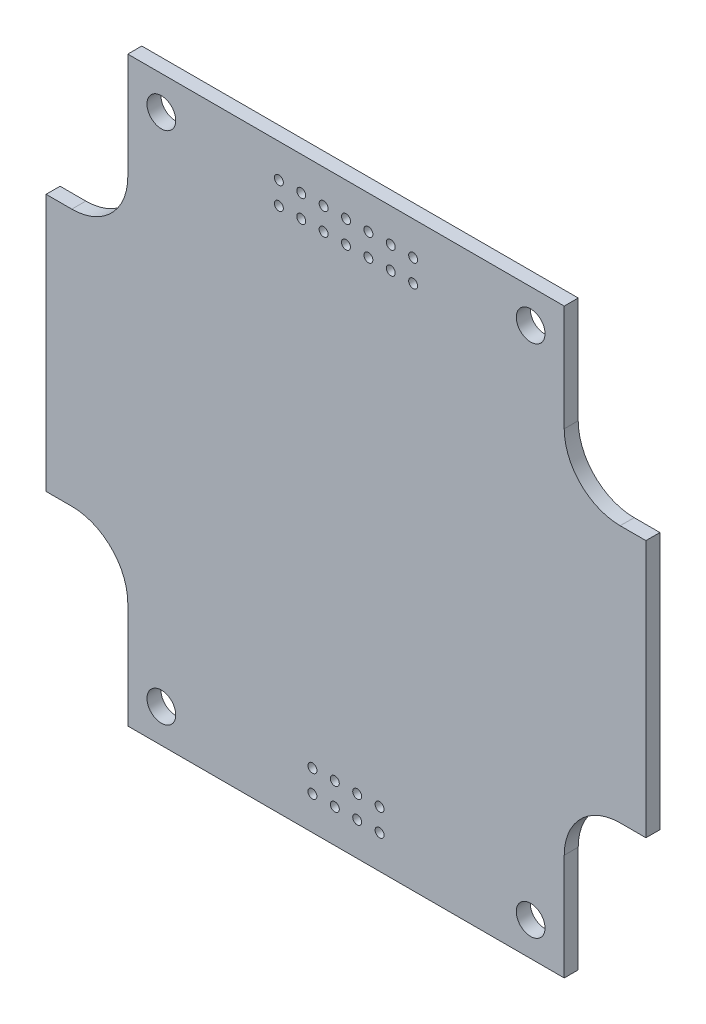
SolidWorks part; units mm, degrees
ref_plane "Front Plane" through (0, 0, 0) normal (0, 0, 1) x (1, 0, 0)
ref_plane "Top Plane" through (0, 0, 0) normal (0, 1, 0) x (1, 0, 0)
ref_plane "Right Plane" through (0, 0, 0) normal (1, 0, 0) x (0, 0, -1)
sketch "Sketch1" plane through (0, 0, 0) normal (0, 0, 1) x (1, 0, 0)
  line L0 (0, 47.625) -> (0, 18.415)
  line L1 (0, 18.415) -> (2.921, 18.415)
  line L2 (9.271, 12.065) -> (9.271, 0)
  line L3 (9.271, 0) -> (58.801, 0)
  line L4 (0, 33.02) -> (34.036, 33.02) construction
  line L5 (34.036, 33.02) -> (34.036, 0) construction
  line L6 (58.801, 12.065) -> (58.801, 0)
  line L7 (68.072, 18.415) -> (65.151, 18.415)
  line L8 (68.072, 47.625) -> (68.072, 18.415)
  line L9 (9.271, 53.975) -> (9.271, 66.04)
  line L10 (0, 47.625) -> (2.921, 47.625)
  line L11 (9.271, 66.04) -> (58.801, 66.04)
  line L12 (68.072, 47.625) -> (65.151, 47.625)
  line L13 (58.801, 53.975) -> (58.801, 66.04)
  arc A0 (2.921, 18.415) -> (9.271, 12.065) centre (2.921, 12.065) cw
  arc A1 (65.151, 18.415) -> (58.801, 12.065) centre (65.151, 12.065) ccw
  arc A2 (58.801, 53.975) -> (65.151, 47.625) centre (65.151, 53.975) ccw
  arc A3 (9.271, 53.975) -> (2.921, 47.625) centre (2.921, 53.975) cw
  point P21 (68.072, 33.02)
  point P23 (58.801, 47.625)
  dimension "D5" = 6.35
  dimension "D1" = 24.765
  dimension "D2" = 34.036
  dimension "D3" = 33.02
  dimension "D4" = 14.605
extrude "Boss-Extrude1" add sketch "Sketch1" along normal blind 1.5875
sketch "Sketch3" plane through (0, 0, 1.5875) normal (0, 0, 1) x (1, 0, 0)
  line L113 (0, 33.02) -> (68.072, 33.02) construction
  line L114 (68.072, 33.02) -> (34.036, 33.02) construction
  line L115 (34.036, 33.02) -> (34.036, 66.04) construction
  line L125 (65.151, 18.415) -> (68.072, 18.415)
  line L126 (58.801, 0) -> (58.801, 12.065)
  line L127 (9.271, 0) -> (58.801, 0)
  line L128 (9.271, 12.065) -> (9.271, 0)
  line L129 (0, 18.415) -> (2.921, 18.415)
  line L130 (0, 47.625) -> (0, 18.415)
  line L131 (2.921, 47.625) -> (0, 47.625)
  line L132 (9.271, 66.04) -> (9.271, 53.975)
  line L133 (58.801, 66.04) -> (9.271, 66.04)
  line L134 (68.072, 47.625) -> (65.151, 47.625)
  line L135 (58.801, 53.975) -> (58.801, 66.04)
  line L136 (68.072, 18.415) -> (68.072, 47.625)
  line L137 (65.151, 18.415) -> (68.072, 18.415)
  line L138 (58.801, 0) -> (58.801, 12.065)
  line L139 (9.271, 0) -> (58.801, 0)
  line L140 (9.271, 12.065) -> (9.271, 0)
  line L141 (0, 18.415) -> (2.921, 18.415)
  line L142 (0, 47.625) -> (0, 18.415)
  line L143 (2.921, 47.625) -> (0, 47.625)
  line L144 (9.271, 66.04) -> (9.271, 53.975)
  line L145 (58.801, 66.04) -> (9.271, 66.04)
  line L146 (68.072, 47.625) -> (65.151, 47.625)
  line L147 (58.801, 53.975) -> (58.801, 66.04)
  line L148 (68.072, 18.415) -> (68.072, 47.625)
  circle A36 centre (13.081, 62.23) radius 1.6319
  circle A37 centre (54.991, 62.23) radius 1.632
  circle A38 centre (54.991, 3.81) radius 1.632
  circle A39 centre (13.081, 3.81) radius 1.6319
  arc A40 (65.151, 18.415) -> (58.801, 12.065) centre (65.151, 12.065) ccw
  arc A41 (9.271, 12.065) -> (2.921, 18.415) centre (2.921, 12.065) ccw
  arc A42 (2.921, 47.625) -> (9.271, 53.975) centre (2.921, 53.975) ccw
  arc A43 (58.801, 53.975) -> (65.151, 47.625) centre (65.151, 53.975) ccw
  arc A44 (65.151, 18.415) -> (58.801, 12.065) centre (65.151, 12.065) ccw
  arc A45 (9.271, 12.065) -> (2.921, 18.415) centre (2.921, 12.065) ccw
  arc A46 (2.921, 47.625) -> (9.271, 53.975) centre (2.921, 53.975) ccw
  arc A47 (58.801, 53.975) -> (65.151, 47.625) centre (65.151, 53.975) ccw
  dimension "D2" = 3.2639
  dimension "D3" = 3.81
  dimension "D4" = 3.81
  dimension "D1" = 0
extrude "Cut-Extrude1" cut sketch "Sketch3" against normal through all contours A37 | A38 | A39 | A36 region at (13.081, 62.23, 1.5875) region at (54.991, 62.23, 1.5875) region at (54.991, 3.81, 1.5875) region at (13.081, 3.81, 1.5875)
sketch "Sketch4" plane through (0, 0, 1.5875) normal (0, 0, 1) x (1, 0, 0)
  line L0 (32.004, 65.9195) -> (36.068, 65.9195) construction
  line L1 (36.068, 65.9195) -> (36.068, 56.0005) construction
  line L2 (36.068, 56.0005) -> (32.004, 56.0005) construction
  line L3 (32.004, 56.0005) -> (32.004, 65.9195) construction
  line L4 (34.036, 65.9195) -> (34.036, 56.0005) construction
  line L5 (34.036, 56.0005) -> (32.004, 56.0005) construction
  line L6 (32.004, 56.0005) -> (32.004, 60.96) construction
  line L7 (32.004, 60.96) -> (36.068, 60.96) construction
  line L8 (0, 33.02) -> (68.072, 33.02) construction
  line L9 (0, 47.625) -> (0, 18.415) construction
  line L10 (68.072, 18.415) -> (68.072, 47.625) construction
  line L11 (34.036, 66.04) -> (34.036, 33.02) construction
  line L12 (58.801, 66.04) -> (9.271, 66.04) construction
  line L13 (34.036, 33.02) -> (34.036, 0) construction
  line L14 (9.271, 0) -> (58.801, 0) construction
  line L15 (34.036, 5.08) -> (-49965.964, 5.08) construction
  circle A0 centre (34.036, 62.23) radius 0.508
  circle A1 centre (36.576, 62.23) radius 0.508
  circle A2 centre (39.116, 62.23) radius 0.508
  circle A3 centre (41.656, 62.23) radius 0.508
  circle A4 centre (36.576, 59.69) radius 0.508
  circle A5 centre (39.116, 59.69) radius 0.508
  circle A6 centre (41.656, 59.69) radius 0.508
  circle A7 centre (34.036, 59.69) radius 0.508
  circle A8 centre (31.496, 62.23) radius 0.508
  circle A9 centre (28.956, 62.23) radius 0.508
  circle A10 centre (26.416, 62.23) radius 0.508
  circle A11 centre (31.496, 59.69) radius 0.508
  circle A12 centre (28.956, 59.69) radius 0.508
  circle A13 centre (26.416, 59.69) radius 0.508
  circle A14 centre (34.036, 59.69) radius 0.508
  circle A15 centre (30.226, 6.35) radius 0.508
  circle A16 centre (32.766, 6.35) radius 0.508
  circle A17 centre (35.306, 6.35) radius 0.508
  circle A18 centre (37.846, 6.35) radius 0.508
  circle A19 centre (32.766, 3.81) radius 0.508
  circle A20 centre (35.306, 3.81) radius 0.508
  circle A21 centre (37.846, 3.81) radius 0.508
  circle A22 centre (30.226, 3.81) radius 0.508
  dimension "D1" = 1.016
  dimension "D4" = 4
  dimension "D2" = 0
  dimension "D3" = 1.27
  dimension "D8" = 0
  dimension "D9" = 27.94
  dimension "D10" = 27.94
  dimension "D11" = 1.27
  dimension "D12" = 3.81
  dimension "D5" = 2
  dimension "D6" = 4
  dimension "D7" = 2
  dimension "D13" = 4
  dimension "D14" = 2
extrude "Cut-Extrude2" cut sketch "Sketch4" against normal through all contours A0 | A7 | A10 | A13 | A9 | A12 | A11 | A4 | A5 | A6 | A3 | A2 | A1 | A8 | A21 | A18 | A17 | A20 | A19 | A16 | A15 | A22 region at (34.036, 62.23, 1.5875) region at (36.576, 62.23, 1.5875) region at (39.116, 62.23, 1.5875) region at (41.656, 62.23, 1.5875) region at (36.576, 59.69, 1.5875) region at (39.116, 59.69, 1.5875) region at (41.656, 59.69, 1.5875) region at (34.036, 59.69, 1.5875) region at (31.496, 62.23, 1.5875) region at (28.956, 62.23, 1.5875) region at (26.416, 62.23, 1.5875) region at (31.496, 59.69, 1.5875) region at (28.956, 59.69, 1.5875) region at (26.416, 59.69, 1.5875) region at (30.226, 6.35, 1.5875) region at (32.766, 6.35, 1.5875) region at (35.306, 6.35, 1.5875) region at (37.846, 6.35, 1.5875) region at (32.766, 3.81, 1.5875) region at (35.306, 3.81, 1.5875) region at (37.846, 3.81, 1.5875) region at (30.226, 3.81, 1.5875)
